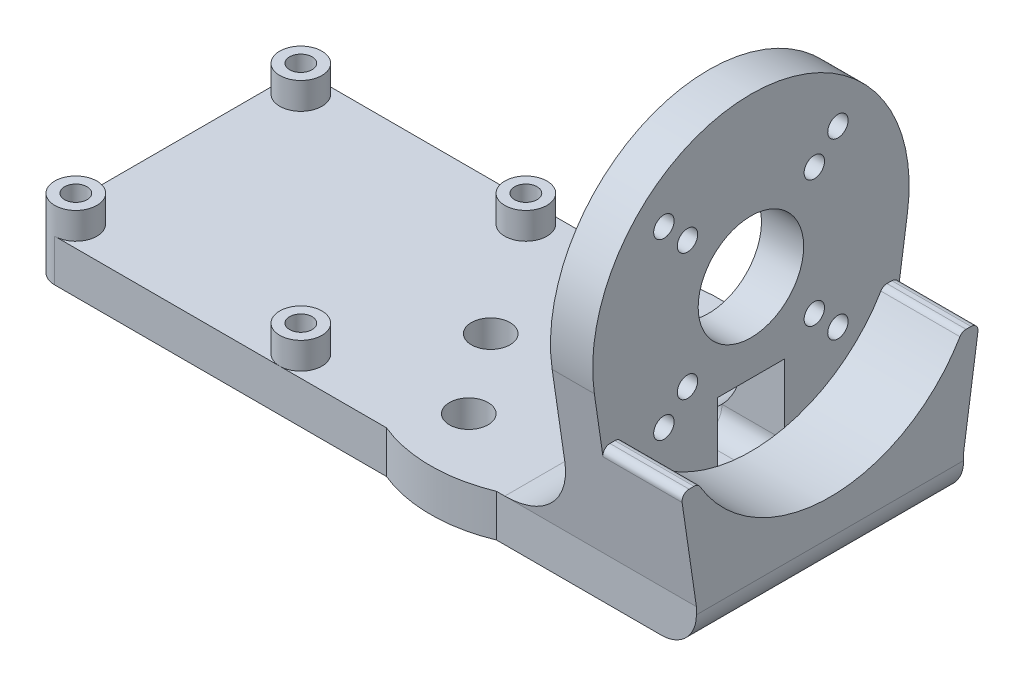
SolidWorks part; units mm, degrees
ref_plane "Front Plane" through (0, 0, 0) normal (0, 0, 1) x (1, 0, 0)
ref_plane "Top Plane" through (0, 0, 0) normal (0, 1, 0) x (1, 0, 0)
ref_plane "Right Plane" through (0, 0, 0) normal (1, 0, 0) x (0, 0, -1)
sketch "Sketch1" plane through (0, 18, 0) normal (0, 1, 0) x (1, 0, 0)
  circle A1 centre (0, 0) radius 20.55
  circle A2 centre (0, 0) radius 20.55
  dimension "D1" = 0
extrude "Boss-Extrude1" add sketch "Sketch1" along normal blind 6
sketch "Sketch12" plane through (0, 24, 0) normal (0, 1, 0) x (1, 0, 0)
  line L1 (-58, 19) -> (-20, 19)
  line L2 (-58, 19) -> (-58, -19)
  line L3 (-58, -19) -> (-20, -19)
  line L4 (-20, 19) -> (-20, -19) construction
  line L5 (-20, 19) -> (25, 19)
  line L6 (-20, 19) -> (-20, -19) construction
  line L7 (-20, -19) -> (25, -19)
  line L8 (25, 19) -> (25, -19)
  point P4 (-20, 0)
  dimension "D1" = 38
  dimension "D2" = 20
  dimension "D3" = 45
extrude "Boss-Extrude5" add sketch "Sketch12" against normal up to surface (6 mm away) contours L7 L8 L5 L1 L2 L3 up to face at (-20.55, 18, 0)
sketch "Sketch5" plane through (0, 18, 0) normal (0, 1, 0) x (1, 0, 0)
  circle A0 centre (-12, 0) radius 2.75
  circle A1 centre (-3.7082, 11.4127) radius 2.75
  circle A2 centre (9.7082, 7.0534) radius 2.75
  circle A3 centre (-3.7082, -11.4127) radius 2.75
  circle A4 centre (9.7082, -7.0534) radius 2.75
  dimension "D1" = 5.5
extrude "Cut-Extrude1" cut sketch "Sketch5" along normal up to surface (6 mm away) up to face at (-8.25, 24, 0)
fillet "Fillet3" radius 3 2 edges at (-58, 21, 19) (-58, 21, -19)
sketch "Sketch15" plane through (0, 24, 0) normal (0, 1, 0) x (1, 0, 0)
  circle A0 centre (-55, 16) radius 3
  circle A1 centre (-23, 16) radius 3
  circle A2 centre (-23, -16) radius 3
  circle A3 centre (-55, -16) radius 3
  dimension "D1" = 6
extrude "Boss-Extrude6" add sketch "Sketch15" along normal up to surface (3.8 mm away)
sketch "Sketch16" plane through (0, 27.8, 0) normal (0, 1, 0) x (1, 0, 0)
  circle A0 centre (-55, 16) radius 1.6
  circle A1 centre (-23, 16) radius 1.6
  circle A2 centre (-23, -16) radius 1.6
  circle A3 centre (-55, -16) radius 1.6
  dimension "D1" = 3.2
extrude "Cut-Extrude7" cut sketch "Sketch16" against normal blind 4.3
sketch "Sketch20" plane through (25, 0, 0) normal (1, 0, 0) x (0, 0, -1)
  line L0 (19, 24) -> (-19, 24) construction
  line L1 (-19, 24) -> (-22.2617, 46.2342)
  line L2 (19, 24) -> (22.2617, 46.2342)
  line L3 (19, 24) -> (-19, 24)
  arc A0 (22.2617, 46.2342) -> (-22.2617, 46.2342) centre (0, 49.5) ccw
  arc A1 (-22.2617, 46.2342) -> (22.2617, 46.2342) centre (0, 49.5) ccw construction
  point P1 (0, 0)
  dimension "D1" = 45
  dimension "D2" = 25.5
extrude "Boss-Extrude7" add sketch "Sketch20" against normal blind 6
sketch "Sketch22" plane through (25, 0, 0) normal (1, 0, 0) x (0, 0, -1)
  line L0 (-21.2005, 39) -> (-18.7617, 39)
  line L1 (21.2005, 39) -> (22.2617, 46.2342) construction
  line L2 (-22.2617, 46.2342) -> (-21.2005, 39) construction
  line L3 (-18.7617, 39) -> (18.7617, 39) construction
  line L4 (18.7617, 39) -> (21.2005, 39)
  line L5 (-19, 24) -> (-19, 18)
  line L6 (-19, 18) -> (19, 18)
  line L7 (19, 18) -> (19, 24)
  line L8 (19, 24) -> (22.2617, 46.2342)
  line L9 (-22.2617, 46.2342) -> (-19, 24)
  line L10 (-19, 24) -> (-19, 18)
  line L11 (-19, 18) -> (19, 18)
  line L12 (19, 18) -> (19, 24)
  line L13 (19, 24) -> (21.2005, 39)
  line L14 (-21.2005, 39) -> (-19, 24)
  arc A0 (-18.7617, 39) -> (18.7617, 39) centre (0, 49.5) ccw
  arc A1 (22.2617, 46.2342) -> (-22.2617, 46.2342) centre (0, 49.5) ccw
  arc A2 (22.2617, 46.2342) -> (-22.2617, 46.2342) centre (0, 49.5) ccw construction
  arc A3 (18.7617, 39) -> (-18.7617, 39) centre (0, 49.5) ccw construction
  point P4 (19, 38.8236)
  point P6 (0, 0)
  point P11 (0, 39)
  point P12 (0, 0)
  dimension "D2" = 43
  dimension "D3" = 15
  dimension "D1" = 0
extrude "Boss-Extrude8" add sketch "Sketch22" along normal blind 11.25
fillet "Fillet4" radius 1 4 edges at (30.625, 39, -21.2005) (30.625, 39, -18.7617) (30.625, 39, 18.7617) (30.625, 39, 21.2005)
fillet "Fillet5" radius 5 1 edges at (36.25, 18, 0)
fillet "Fillet6" radius 10 1 edges at (19, 24, 0)
sketch "Sketch24" plane through (25, 0, 0) normal (-1, 0, 0) x (0, 0, 1)
  line L0 (-16, 24) -> (16, 24) construction
  line L1 (-4.75, 37) -> (4.75, 37)
  line L2 (-4.75, 37) -> (-4.75, 24)
  line L3 (-4.75, 24) -> (4.75, 24)
  line L4 (4.75, 37) -> (4.75, 24)
  arc A0 (2.5, 35.2029) -> (2.5, 33.2029) centre (2.5, 34.2029) ccw construction
  arc A1 (2.5, 33.2029) -> (2.5, 35.2029) centre (2.5, 34.2029) ccw construction
  arc A2 (0, 35) -> (0, 33) centre (0, 34) ccw construction
  arc A3 (0, 33) -> (0, 35) centre (0, 34) ccw construction
  arc A4 (-2.5, 35.2029) -> (-2.5, 33.2029) centre (-2.5, 34.2029) ccw construction
  arc A5 (-2.5, 33.2029) -> (-2.5, 35.2029) centre (-2.5, 34.2029) ccw construction
  arc A6 (-12.3744, 62.8744) -> (-12.3744, 60.8744) centre (-12.3744, 61.8744) ccw construction
  arc A7 (-12.3744, 60.8744) -> (-12.3744, 62.8744) centre (-12.3744, 61.8744) ccw construction
  arc A8 (-9.0156, 59.5156) -> (-9.0156, 57.5156) centre (-9.0156, 58.5156) ccw construction
  arc A9 (-9.0156, 57.5156) -> (-9.0156, 59.5156) centre (-9.0156, 58.5156) ccw construction
  arc A10 (12.3744, 62.8744) -> (12.3744, 60.8744) centre (12.3744, 61.8744) ccw construction
  arc A11 (12.3744, 60.8744) -> (12.3744, 62.8744) centre (12.3744, 61.8744) ccw construction
  arc A12 (9.0156, 59.5156) -> (9.0156, 57.5156) centre (9.0156, 58.5156) ccw construction
  arc A13 (9.0156, 57.5156) -> (9.0156, 59.5156) centre (9.0156, 58.5156) ccw construction
  arc A14 (12.3744, 38.1256) -> (12.3744, 36.1256) centre (12.3744, 37.1256) ccw construction
  arc A15 (12.3744, 36.1256) -> (12.3744, 38.1256) centre (12.3744, 37.1256) ccw construction
  arc A16 (9.0156, 41.4844) -> (9.0156, 39.4844) centre (9.0156, 40.4844) ccw construction
  arc A17 (9.0156, 39.4844) -> (9.0156, 41.4844) centre (9.0156, 40.4844) ccw construction
  arc A18 (-12.3744, 38.1256) -> (-12.3744, 36.1256) centre (-12.3744, 37.1256) ccw construction
  arc A19 (-12.3744, 36.1256) -> (-12.3744, 38.1256) centre (-12.3744, 37.1256) ccw construction
  arc A20 (-9.0156, 41.4844) -> (-9.0156, 39.4844) centre (-9.0156, 40.4844) ccw construction
  arc A21 (-9.0156, 39.4844) -> (-9.0156, 41.4844) centre (-9.0156, 40.4844) ccw construction
  arc A22 (2.5, 35.2029) -> (2.5, 33.2029) centre (2.5, 34.2029) ccw construction
  arc A23 (2.5, 33.2029) -> (2.5, 35.2029) centre (2.5, 34.2029) ccw construction
  arc A24 (0, 35) -> (0, 33) centre (0, 34) ccw construction
  arc A25 (0, 33) -> (0, 35) centre (0, 34) ccw construction
  arc A26 (-2.5, 35.2029) -> (-2.5, 33.2029) centre (-2.5, 34.2029) ccw construction
  arc A27 (-2.5, 33.2029) -> (-2.5, 35.2029) centre (-2.5, 34.2029) ccw construction
  arc A28 (-12.3744, 62.8744) -> (-12.3744, 60.8744) centre (-12.3744, 61.8744) ccw construction
  arc A29 (-12.3744, 60.8744) -> (-12.3744, 62.8744) centre (-12.3744, 61.8744) ccw construction
  arc A30 (-9.0156, 59.5156) -> (-9.0156, 57.5156) centre (-9.0156, 58.5156) ccw construction
  arc A31 (-9.0156, 57.5156) -> (-9.0156, 59.5156) centre (-9.0156, 58.5156) ccw construction
  arc A32 (12.3744, 62.8744) -> (12.3744, 60.8744) centre (12.3744, 61.8744) ccw construction
  arc A33 (12.3744, 60.8744) -> (12.3744, 62.8744) centre (12.3744, 61.8744) ccw construction
  arc A34 (9.0156, 59.5156) -> (9.0156, 57.5156) centre (9.0156, 58.5156) ccw construction
  arc A35 (9.0156, 57.5156) -> (9.0156, 59.5156) centre (9.0156, 58.5156) ccw construction
  arc A36 (12.3744, 38.1256) -> (12.3744, 36.1256) centre (12.3744, 37.1256) ccw construction
  arc A37 (12.3744, 36.1256) -> (12.3744, 38.1256) centre (12.3744, 37.1256) ccw construction
  arc A38 (9.0156, 41.4844) -> (9.0156, 39.4844) centre (9.0156, 40.4844) ccw construction
  arc A39 (9.0156, 39.4844) -> (9.0156, 41.4844) centre (9.0156, 40.4844) ccw construction
  arc A40 (-12.3744, 38.1256) -> (-12.3744, 36.1256) centre (-12.3744, 37.1256) ccw construction
  arc A41 (-12.3744, 36.1256) -> (-12.3744, 38.1256) centre (-12.3744, 37.1256) ccw construction
  arc A42 (-9.0156, 41.4844) -> (-9.0156, 39.4844) centre (-9.0156, 40.4844) ccw construction
  arc A43 (-9.0156, 39.4844) -> (-9.0156, 41.4844) centre (-9.0156, 40.4844) ccw construction
  arc A44 (22.2617, 46.2342) -> (-22.2617, 46.2342) centre (0, 49.5) ccw construction
  arc A45 (22.2617, 46.2342) -> (-22.2617, 46.2342) centre (0, 49.5) ccw construction
  circle A46 centre (0, 49.5) radius 7.5
  point P44 (0, 24)
  dimension "D1" = 15
  dimension "D2" = 9.5
  dimension "D3" = 13
extrude "Cut-Extrude8" cut sketch "Sketch24" along normal through all
sketch "Sketch25" plane through (25, 0, 0) normal (1, 0, 0) x (0, 0, -1)
  arc A0 (-12.3744, 60.8744) -> (-12.3744, 62.8744) centre (-12.3744, 61.8744) ccw construction
  arc A1 (-12.3744, 62.8744) -> (-12.3744, 60.8744) centre (-12.3744, 61.8744) ccw construction
  arc A2 (12.3744, 60.8744) -> (12.3744, 62.8744) centre (12.3744, 61.8744) ccw construction
  arc A3 (12.3744, 62.8744) -> (12.3744, 60.8744) centre (12.3744, 61.8744) ccw construction
  arc A4 (9.0156, 57.5156) -> (9.0156, 59.5156) centre (9.0156, 58.5156) ccw construction
  arc A5 (9.0156, 59.5156) -> (9.0156, 57.5156) centre (9.0156, 58.5156) ccw construction
  arc A6 (12.3744, 36.1256) -> (12.3744, 38.1256) centre (12.3744, 37.1256) ccw construction
  arc A7 (12.3744, 38.1256) -> (12.3744, 36.1256) centre (12.3744, 37.1256) ccw construction
  arc A8 (9.0156, 39.4844) -> (9.0156, 41.4844) centre (9.0156, 40.4844) ccw construction
  arc A9 (9.0156, 41.4844) -> (9.0156, 39.4844) centre (9.0156, 40.4844) ccw construction
  arc A10 (-12.3744, 36.1256) -> (-12.3744, 38.1256) centre (-12.3744, 37.1256) ccw construction
  arc A11 (-12.3744, 38.1256) -> (-12.3744, 36.1256) centre (-12.3744, 37.1256) ccw construction
  arc A12 (-9.0156, 39.4844) -> (-9.0156, 41.4844) centre (-9.0156, 40.4844) ccw construction
  arc A13 (-9.0156, 41.4844) -> (-9.0156, 39.4844) centre (-9.0156, 40.4844) ccw construction
  arc A14 (-9.0156, 57.5156) -> (-9.0156, 59.5156) centre (-9.0156, 58.5156) ccw construction
  arc A15 (-9.0156, 59.5156) -> (-9.0156, 57.5156) centre (-9.0156, 58.5156) ccw construction
  arc A16 (-12.3744, 60.8744) -> (-12.3744, 62.8744) centre (-12.3744, 61.8744) ccw construction
  arc A17 (-12.3744, 62.8744) -> (-12.3744, 60.8744) centre (-12.3744, 61.8744) ccw construction
  arc A18 (12.3744, 60.8744) -> (12.3744, 62.8744) centre (12.3744, 61.8744) ccw construction
  arc A19 (12.3744, 62.8744) -> (12.3744, 60.8744) centre (12.3744, 61.8744) ccw construction
  arc A20 (9.0156, 57.5156) -> (9.0156, 59.5156) centre (9.0156, 58.5156) ccw construction
  arc A21 (9.0156, 59.5156) -> (9.0156, 57.5156) centre (9.0156, 58.5156) ccw construction
  arc A22 (12.3744, 36.1256) -> (12.3744, 38.1256) centre (12.3744, 37.1256) ccw construction
  arc A23 (12.3744, 38.1256) -> (12.3744, 36.1256) centre (12.3744, 37.1256) ccw construction
  arc A24 (9.0156, 39.4844) -> (9.0156, 41.4844) centre (9.0156, 40.4844) ccw construction
  arc A25 (9.0156, 41.4844) -> (9.0156, 39.4844) centre (9.0156, 40.4844) ccw construction
  arc A26 (-12.3744, 36.1256) -> (-12.3744, 38.1256) centre (-12.3744, 37.1256) ccw construction
  arc A27 (-12.3744, 38.1256) -> (-12.3744, 36.1256) centre (-12.3744, 37.1256) ccw construction
  arc A28 (-9.0156, 39.4844) -> (-9.0156, 41.4844) centre (-9.0156, 40.4844) ccw construction
  arc A29 (-9.0156, 41.4844) -> (-9.0156, 39.4844) centre (-9.0156, 40.4844) ccw construction
  arc A30 (-9.0156, 57.5156) -> (-9.0156, 59.5156) centre (-9.0156, 58.5156) ccw construction
  arc A31 (-9.0156, 59.5156) -> (-9.0156, 57.5156) centre (-9.0156, 58.5156) ccw construction
  circle A32 centre (12.3744, 61.8744) radius 1.45
  circle A33 centre (9.0156, 58.5156) radius 1.45
  circle A34 centre (-9.0156, 58.5156) radius 1.45
  circle A35 centre (-12.3744, 61.8744) radius 1.45
  circle A36 centre (-9.0156, 40.4844) radius 1.45
  circle A37 centre (-12.3744, 37.1256) radius 1.45
  circle A38 centre (9.0156, 40.4844) radius 1.45
  circle A39 centre (12.3744, 37.1256) radius 1.45
  dimension "D1" = 2.9
extrude "Cut-Extrude9" cut sketch "Sketch25" against normal up to surface (6 mm away) up to face at (19, 41.0293, 0)
fillet "Fillet7" radius 3 3 edges at (18.1052, 24, -4.75) (18.1052, 24, 4.75) (25, 24, 0)
equation "\"M5_CLRNCE\"=5.5"
equation "\"FLANGE_TH\" =6"
equation "\"D1@Boss-Extrude1\"=\"FLANGE_TH\""
equation "\"D1@Sketch5\"=\"M5_CLRNCE\""
equation "\"MOTOR_OFFSET\"= 45"
equation "\"MOTOR_H_OFFSET\"=0"
equation "\"D1@Boss-Extrude2\"=\"MOTOR_H_OFFSET\""
equation "\"M2.5_INSERT_DIAM\"=3.2"
equation "\"D1@Sketch16\"=\"M2.5_INSERT_DIAM\""
equation "\"M2.5_INSERT_DEPTH\"=4.3"
equation "\"D1@Cut-Extrude7\"=\"M2.5_INSERT_DEPTH\""
equation "\"D2@Sketch20\"=45/2+3"
equation "\"D1@Boss-Extrude8\"=22.5/2"
equation "\"M2.5_CLRNCE\"=2.9"
equation "\"D1@Sketch25\"=\"M2.5_CLRNCE\""
